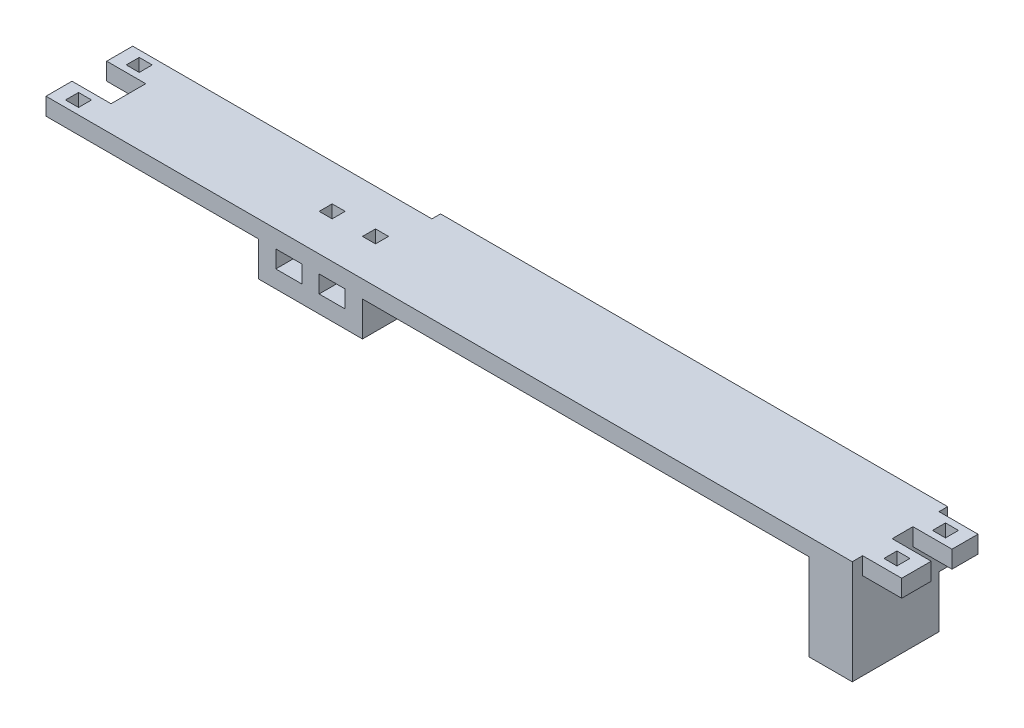
SolidWorks part; units mm, degrees
ref_plane "Front Plane" through (0, 0, 0) normal (0, 0, 1) x (1, 0, 0)
ref_plane "Top Plane" through (0, 0, 0) normal (0, 1, 0) x (1, 0, 0)
ref_plane "Right Plane" through (0, 0, 0) normal (1, 0, 0) x (0, 0, -1)
sketch "Sketch2" plane through (0, 0, 0) normal (0, 1, 0) x (1, 0, 0)
  line L1 (0, 0) -> (194.96, 0)
  line L2 (0, 0) -> (0, 6)
  line L3 (0, 6) -> (194.96, 6)
  line L4 (194.96, 0) -> (194.96, 6)
  dimension "D1" = 194.96
  dimension "D2" = 6
extrude "Boss-Extrude1" add sketch "Sketch2" along normal blind 4
sketch "Sketch3" plane through (0, 0, 0) normal (0, 0, -1) x (-1, 0, 0)
  line L0 (-194.96, 4) -> (0, 4) construction
  line L1 (-9, 4) -> (-185.96, 4)
  line L2 (-9, 4) -> (-9, 0)
  line L3 (-9, 0) -> (-185.96, 0)
  line L4 (-185.96, 4) -> (-185.96, 0)
  line L5 (-194.96, 0) -> (0, 0) construction
  line L7 (-194.96, 4) -> (-194.96, 0) construction
  line L8 (0, 4) -> (0, 0) construction
  dimension "D1" = 9
  dimension "D2" = 9
extrude "Boss-Extrude2" add sketch "Sketch3" against normal blind 14
sketch "Sketch4" plane through (9, 0, 0) normal (-1, 0, 0) x (0, 0, 1)
  line L0 (14, 0) -> (0, 0) construction
  line L1 (14, 4) -> (8, 4)
  line L2 (14, 4) -> (14, 0)
  line L3 (14, 0) -> (8, 0)
  line L4 (8, 4) -> (8, 0)
  line L6 (0, 0) -> (0, 4) construction
  dimension "D1" = 6
extrude "Boss-Extrude3" add sketch "Sketch4" along normal blind 9
sketch "Sketch5" plane through (185.96, 0, 0) normal (1, 0, 0) x (0, 0, -1)
  line L0 (-14, 4) -> (0, 4) construction
  line L1 (-11.6, 4) -> (-4.8, 4)
  line L2 (-11.6, 4) -> (-11.6, 0)
  line L3 (-11.6, 0) -> (-4.8, 0)
  line L4 (-4.8, 4) -> (-4.8, 0)
  line L5 (-14, 0) -> (0, 0) construction
  line L6 (-14, 4) -> (-14, 0) construction
  line L7 (0, 4) -> (0, 0) construction
  dimension "D1" = 2.4
  dimension "D2" = 4.8
extrude "Boss-Extrude4" add sketch "Sketch5" along normal blind 9
sketch "Sketch6" plane through (0, 4, 0) normal (0, 1, 0) x (1, 0, 0)
  line L0 (0, 6) -> (0, 0) construction
  line L1 (3, 4.5) -> (6, 4.5)
  line L2 (3, 4.5) -> (3, 1.5)
  line L3 (3, 1.5) -> (6, 1.5)
  line L4 (6, 4.5) -> (6, 1.5)
  line L5 (194.96, 6) -> (0, 6) construction
  line L7 (0, -14) -> (185.96, -14) construction
  line L8 (3, -9.5) -> (6, -9.5)
  line L9 (3, -9.5) -> (3, -12.5)
  line L10 (3, -12.5) -> (6, -12.5)
  line L11 (6, -9.5) -> (6, -12.5)
  line L12 (0, -14) -> (0, -8) construction
  line L13 (194.96, 0) -> (194.96, 6) construction
  line L14 (188.96, 4.5) -> (191.96, 4.5)
  line L15 (188.96, 4.5) -> (188.96, 1.5)
  line L16 (188.96, 1.5) -> (191.96, 1.5)
  line L17 (191.96, 4.5) -> (191.96, 1.5)
  line L18 (194.96, -4.8) -> (194.96, -11.6) construction
  line L19 (191.96, -6.7) -> (188.96, -6.7)
  line L20 (191.96, -6.7) -> (191.96, -9.7)
  line L21 (191.96, -9.7) -> (188.96, -9.7)
  line L22 (188.96, -6.7) -> (188.96, -9.7)
  line L23 (194.96, -4.8) -> (185.96, -4.8) construction
  dimension "D1" = 3
  dimension "D2" = 3
  dimension "D3" = 3
  dimension "D4" = 1.5
  dimension "D5" = 3
  dimension "D6" = 1.5
  dimension "D7" = 3
  dimension "D8" = 1.5
  dimension "D9" = 3
  dimension "D10" = 3
  dimension "D11" = 3
  dimension "D12" = 3
  dimension "D13" = 3
  dimension "D14" = 3
  dimension "D15" = 1.9
extrude "Cut-Extrude1" cut sketch "Sketch6" against normal up to next
sketch "Sketch7" plane through (0, 0, 0) normal (0, -1, 0) x (1, 0, 0)
  line L0 (194.96, -6) -> (0, -6) construction
  line L1 (185.96, 14) -> (175.96, 14)
  line L2 (185.96, 14) -> (185.96, -6)
  line L3 (185.96, -6) -> (175.96, -6)
  line L4 (175.96, 14) -> (175.96, -6)
  dimension "D1" = 10
extrude "Boss-Extrude5" add sketch "Sketch7" along normal blind 20
sketch "Sketch8" plane through (0, 0, 0) normal (0, -1, 0) x (1, 0, 0)
  line L0 (175.96, -6) -> (0, -6) construction
  line L1 (49, -6) -> (185.96, -6)
  line L2 (49, -6) -> (49, 0)
  line L3 (49, 0) -> (185.96, 0)
  line L4 (185.96, -6) -> (185.96, 0)
  line L5 (185.96, -6) -> (185.96, 14) construction
  line L6 (9, 8) -> (9, 0) construction
  dimension "D1" = 40
  dimension "D2" = 6
extrude "Boss-Extrude6" add sketch "Sketch8" along normal blind 8
chamfer "Chamfer1" distance 12 angle 50 1 edges at (175.96, -8, -3) first distance on face at (175.96, -9.3333, 2.6667)
sketch "Sketch9" plane through (0, 0, 0) normal (0, 0, 1) x (1, 0, 0)
  line L0 (175.96, 0) -> (0, 0) construction
  line L1 (49, -8) -> (55, -8)
  line L2 (49, -8) -> (49, 0)
  line L3 (49, 0) -> (55, 0)
  line L5 (161.659, -8) -> (49, -8) construction
  line L6 (61, -8) -> (73, -8)
  line L8 (61, 0) -> (73, 0)
  line L9 (73, -8) -> (73, 0)
  line L10 (175.96, 0) -> (49, 0) construction
  line L11 (55, 0) -> (61, 0)
  line L12 (55, -8) -> (61, -8)
  dimension "D1" = 24
extrude "Boss-Extrude7" add sketch "Sketch9" along normal up to surface (14 mm away) up to face at (120.64, -5.3333, 14)
sketch "Sketch10" plane through (0, 0, 14) normal (0, 0, 1) x (1, 0, 0)
  line L0 (49, 0) -> (0, 0) construction
  line L1 (53, 0) -> (59, 0)
  line L2 (53, 0) -> (53, -4)
  line L3 (53, -4) -> (59, -4)
  line L4 (59, 0) -> (59, -4)
  line L5 (49, 0) -> (49, -8) construction
  line L7 (63, 0) -> (69, 0)
  line L8 (63, 0) -> (63, -4)
  line L9 (63, -4) -> (69, -4)
  line L10 (69, 0) -> (69, -4)
  dimension "D1" = 6
  dimension "D2" = 4
  dimension "D3" = 0
  dimension "D4" = 4
  dimension "D5" = 6
  dimension "D6" = 4
extrude "Cut-Extrude2" cut sketch "Sketch10" against normal up to next
sketch "Sketch11" plane through (0, 4, 0) normal (0, 1, 0) x (1, 0, 0)
  line L0 (53, 6) -> (53, -14) construction
  line L1 (54.5, -2.5) -> (57.5, -2.5)
  line L2 (54.5, -2.5) -> (54.5, -5.5)
  line L3 (54.5, -5.5) -> (57.5, -5.5)
  line L4 (57.5, -2.5) -> (57.5, -5.5)
  line L5 (0, -14) -> (185.96, -14) construction
  line L8 (63, 6) -> (63, -14) construction
  line L9 (64.5, -5.5) -> (67.5, -5.5)
  line L10 (64.5, -5.5) -> (64.5, -2.5)
  line L11 (64.5, -2.5) -> (67.5, -2.5)
  line L12 (67.5, -5.5) -> (67.5, -2.5)
  dimension "D1" = 1.5
  dimension "D2" = 3
  dimension "D3" = 3
  dimension "D4" = 8.5
  dimension "D5" = 3
  dimension "D6" = 3
  dimension "D7" = 1.5
  dimension "D8" = 8.5
extrude "Cut-Extrude3" cut sketch "Sketch11" against normal up to next
sketch "Sketch12" plane through (0, 0, -6) normal (0, 0, -1) x (-1, 0, 0)
  line L0 (-194.96, 4) -> (0, 4) construction
  line L1 (-185.96, 4) -> (-69, 4)
  line L2 (-185.96, 4) -> (-185.96, -8)
  line L3 (-185.96, -8) -> (-69, -8)
  line L4 (-69, 4) -> (-69, -8)
  line L5 (-49, -8) -> (-161.659, -8) construction
  line L6 (-185.96, -20) -> (-185.96, 0) construction
  line L7 (-69, 0) -> (-69, -4) construction
  dimension "D1" = 0
  dimension "D2" = 0
extrude "Boss-Extrude8" add sketch "Sketch12" along normal blind 2
